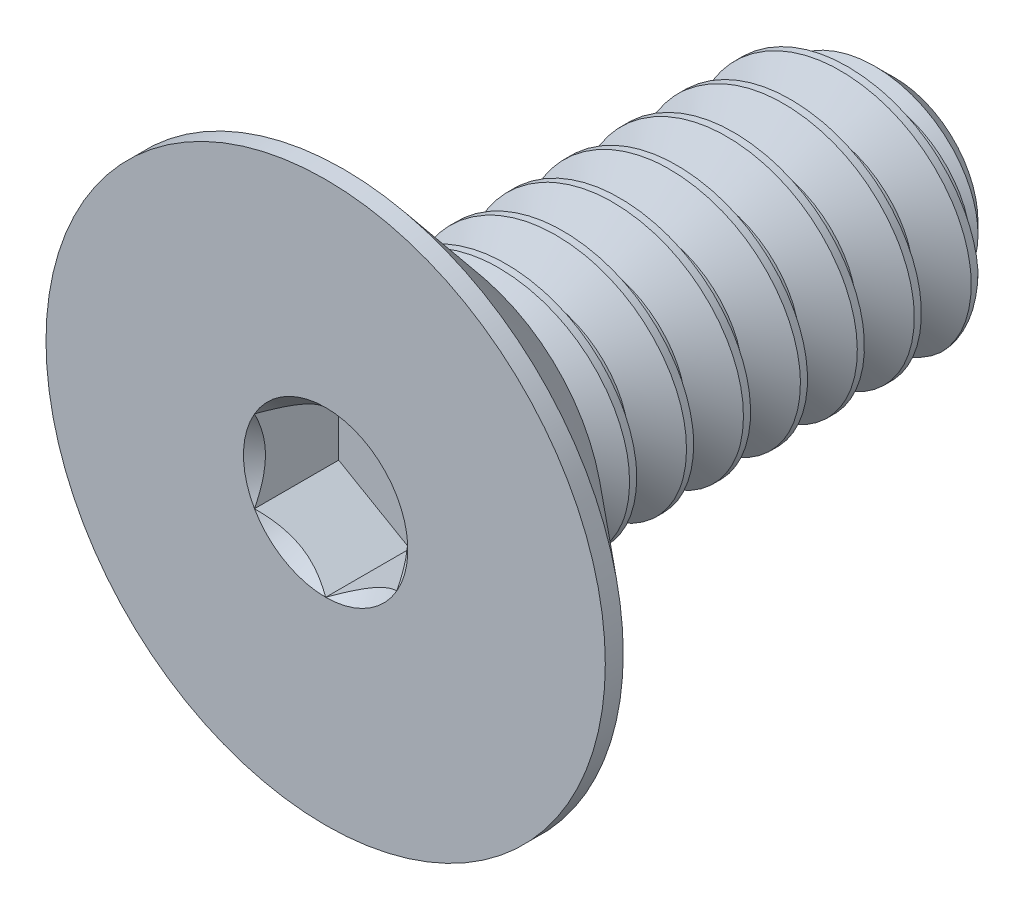
SolidWorks part; units mm, degrees
ref_plane "Front" through (0, 0, 0) normal (0, 0, 1) x (1, 0, 0)
ref_plane "Top" through (0, 0, 0) normal (0, 1, 0) x (1, 0, 0)
ref_plane "Right" through (0, 0, 0) normal (1, 0, 0) x (0, 0, -1)
sketch "Sketch1" plane through (0, 0, 0) normal (1, 0, 0) x (0, 0, -1)
  line L0 (0, 3.8989) -> (0.25, 3.8989) construction
  line L1 (0.25, 3.8989) -> (1.6764, 2.199) construction
  line L2 (0, 1.7526) -> (7.9375, 1.7526)
  line L3 (7.9375, 1.7526) -> (7.9375, 0)
  line L4 (7.9375, 0) -> (0, 0)
  line L5 (0, 0) -> (0, 3.8989) construction
  line L6 (0, 3.8989) -> (0, -3.8989) construction
  line L7 (7.9375, 1.7526) -> (7.9375, -1.7526) construction
  line L8 (0, -3.8989) -> (0.25, -3.8989) construction
  line L9 (0.25, -3.8989) -> (1.6764, -2.199) construction
  line L11 (0, 1.7526) -> (0, 0)
  line L12 (1.6764, 2.199) -> (1.6764, 0) construction
  line L13 (1.6764, -2.199) -> (1.6764, 2.199) construction
  point P15 (0, 0)
  point P17 (7.9375, 0)
  dimension "D1" = 0.25
revolve "Revolve1" add sketch "Sketch1" angle 360 mid plane about L4
sketch "Sketch3" plane through (0, 0, -7.9375) normal (0, 0, -1) x (-1, 0, 0)
  circle A0 centre (0, 0) radius 1.7526
curve "Helix/Spiral1" pitch 0.7937 height 7.9375 radius 1.7526 centre (0, 0, -7.9375) axis (0, 0, 1) start towards (0, 1, 0)
sketch "Sketch2" plane through (0, 0, 0) normal (1, 0, 0) x (0, 0, -1)
  line L0 (7.9375, 1.7526) -> (8.632, 1.7526)
  line L1 (8.632, 1.7526) -> (8.3344, 1.237)
  line L2 (8.3344, 1.237) -> (8.2352, 1.237)
  line L3 (8.2352, 1.237) -> (7.9375, 1.7526)
  line L4 (8.0863, 1.4948) -> (8.4832, 1.4948) construction
  dimension "D1" = 60
  dimension "D2" = 0.0992
  dimension "D3" = 0.3969
chamfer "Chamfer1" distance 0.5953 angle 45 1 edges at (0, 1.7526, -7.9375)
sweep "Cut-Sweep1" cut profiles "Sketch2" path "Helix/Spiral1" align with end faces yes
sketch "Sketch7" plane through (0, 0, 0) normal (1, 0, 0) x (0, 0, -1)
  line L0 (0, 3.8989) -> (0.25, 3.8989) construction
  line L1 (0.25, 3.8989) -> (1.6764, 2.199) construction
  line L2 (0, 3.8989) -> (0.25, 3.8989)
  line L3 (0.25, 3.8989) -> (1.6764, 2.199)
  line L4 (1.6764, 2.199) -> (1.6764, 0) construction
  line L5 (1.6764, 2.199) -> (1.6764, 0)
  line L7 (0, 0) -> (0, 3.8989) construction
  line L8 (0, 0) -> (0, 3.8989)
  line L9 (0, 0) -> (1.6764, 0)
  line L10 (16.5964, 0) -> (-16.5964, 0) construction
revolve "Revolve2" add sketch "Sketch7" angle 360 mid plane about L9
ref_plane "Plane1" through (0, 0, -1.6764) normal (0, 0, 1) x (1, 0, 0)
sketch "Sketch5" plane through (0, 0, 0) normal (0, 0, 1) x (1, 0, 0)
  line L1 (0.9922, -0.5728) -> (0.9922, 0.5728)
  line L2 (0.9922, 0.5728) -> (0, 1.1457)
  line L3 (0, 1.1457) -> (-0.9922, 0.5728)
  line L4 (-0.9922, 0.5728) -> (-0.9922, -0.5728)
  line L5 (-0.9922, -0.5728) -> (0, -1.1457)
  line L6 (0, -1.1457) -> (0.9922, -0.5728)
  circle A0 centre (0, 0) radius 0.9922 construction
  dimension "Hex" = 1.9844
extrude "Cut-Extrude2" cut sketch "Sketch5" against normal blind 1.1735
sketch "Sketch6" plane through (0, 0, 0) normal (0, 0, 1) x (1, 0, 0)
  circle A0 centre (0, 0) radius 1.1457
extrude "Cut-Extrude3" cut sketch "Sketch6" against normal blind 1.1735 draft 45
sketch "Sketch9" [suppressed] plane through (0, 0, -5.5) normal (0, 0, 1) x (1, 0, 0)
  circle A1 centre (0, 0) radius 5
  circle A2 centre (0, 0) radius 5
  point P0 (0, 5)
  dimension "D1" = 0
extrude "Boss-Extrude2" [suppressed] add sketch "Sketch9" against normal offset from surface (18.5 mm away) 26 up to face at (0, 1.1573, -7.9375)
fillet "Fillet1" [suppressed] radius 0.3505
sketch "Sketch10" plane through (0, 0, 0) normal (1, 0, 0) x (0, 0, -1)
  line L0 (7.9375, 1.7526) -> (7.9375, -1.7526) construction
  line L2 (0, 1.7526) -> (7.9375, 1.7526) construction
  line L4 (0.25, -3.8989) -> (1.6764, -2.199) construction
  line L5 (7.9375, -1.1573) -> (7.9375, 1.1573) construction
  line L7 (0.25, 3.8989) -> (1.6764, 2.199) construction
  line L8 (0.25, -3.8989) -> (1.6764, -2.199) construction
  line L9 (0.25, 3.8989) -> (1.6764, 2.199) construction
  point P0 (6.7469, -1.7526)
  point P8 (0, 3.8989)
  point P9 (7.9375, 0)
  point P11 (7.9375, 1.7526)
  point P14 (7.9375, -1.7526)
  point P16 (1.6764, 2.199)
  dimension "D1" = 1.1906
sketch "Sketch11" plane through (0, 0, 0) normal (0, 0, 1) x (1, 0, 0)
  line L0 (-0.9922, -0.5728) -> (-0.9922, 0.5728) construction
  line L1 (0.9922, 0.5728) -> (0.9922, -0.5728) construction
  circle A0 centre (0, 0) radius 3.8989 construction
  point P0 (-0.9922, 0)
  point P1 (0.9922, 0)
  point P4 (3.8989, 0)
  point P7 (-3.8989, 0)
ref_axis "Center Axis 1" through (0, 0, -39.5108) along (0, 0, 1)
ref_plane "Contact Plane 1" through (0, 0, 0) normal (0, 0, 1) x (1, 0, 0)
ref_plane "Contact Plane 2" through (0, 0, -7.9375) normal (0, 0, -1) x (-1, 0, 0)
equation "\"D3@Helix/Spiral1\" = \"Lg@Sketch1\""
equation "\"D2@Sketch2\" = \"D4@Helix/Spiral1\" * .125"
equation "\"D3@Sketch2\" = \"D4@Helix/Spiral1\" * .5"
equation "\"D1@Chamfer1\" = \"D4@Helix/Spiral1\" * .75"
equation "\"D1@Cut-Extrude2\" = \"Head Ht@Sketch1\" * .7"
equation "\"D1@Sketch10\" = \"D4@Helix/Spiral1\" * 1.5"
equation "\"D1@Cut-Extrude3\" = \"D1@Cut-Extrude2\""
equation "\"D1@Fillet1\" = \"Dia@Sketch1\" * .1"
